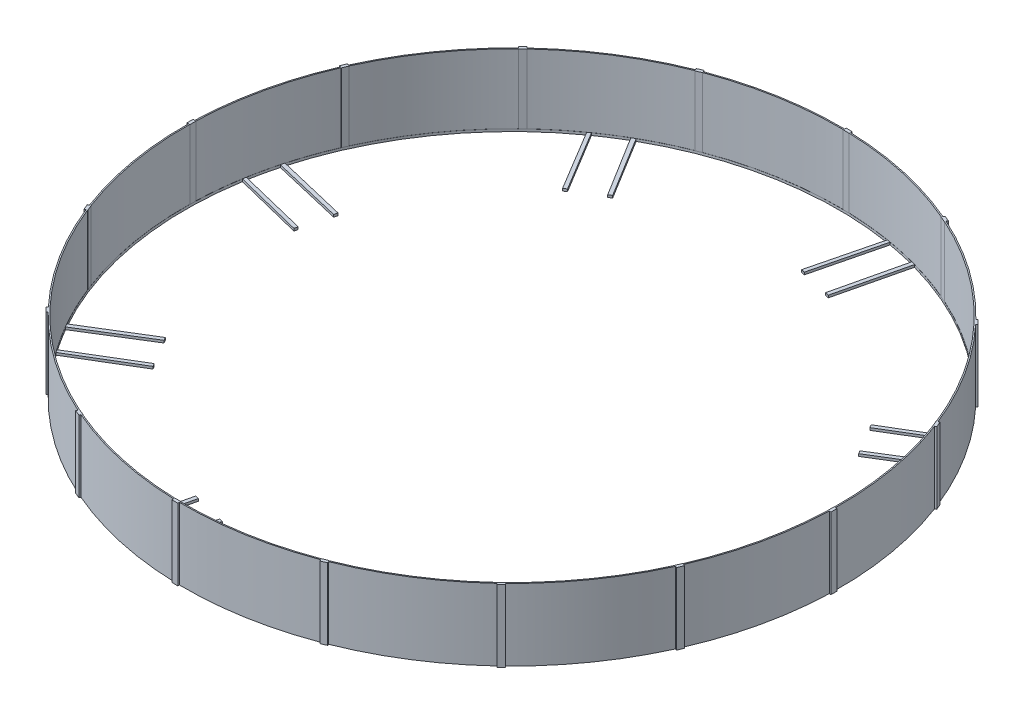
SolidWorks part; units mm, degrees
note: '?' marks a value the reader was unsure of.
ref_plane "Front Plane" through (0, 0, 0) normal (0, 0, 1) x (1, 0, 0)
ref_plane "Top Plane" through (0, 0, 0) normal (0, 1, 0) x (1, 0, 0)
ref_plane "Right Plane" through (0, 0, 0) normal (1, 0, 0) x (0, 0, -1)
sketch "Sketch2" plane through (0, 0, 0) normal (0, 1, 0) x (1, 0, 0)
  circle A0 centre (0, 0) radius 27500
  dimension "D1" = 55000
extrude "Boss-Extrude1" add sketch "Sketch2" along normal blind 6000 contours A0
sketch "Sketch3" plane through (0, 6000, 0) normal (0, 1, 0) x (1, 0, 0)
  circle A0 centre (0, 0) radius 27400
extrude "Cut-Extrude1" cut sketch "Sketch3" against normal blind 5800
ref_plane "Plane1" through (27500, 0, 0) normal (1, 0, 0) x (0, 0, -1)
sketch "Sketch6" plane through (27500, 0, 0) normal (1, 0, 0) x (0, 0, -1)
  line L0 (-387.6781, 6000) -> (-387.6781, 0)
  line L1 (-387.6781, 0) -> (-887.6781, 0)
  line L2 (-887.6781, 0) -> (-887.6781, 6000)
  line L3 (-887.6781, 6000) -> (-387.6781, 6000)
  dimension "D1" = 500
extrude "Boss-Extrude2" add sketch "Sketch6" along normal mid plane 250
pattern_circular "CirPattern1" count 16 over 360 about axis through (-0.0998, 0, -0.0022) along (0, 1, 0) of "Boss-Extrude2"
sketch "Sketch8" plane through (0, 200, 0) normal (0, 1, 0) x (1, 0, 0)
  circle A0 centre (0, 0) radius 27390
extrude "Cut-Extrude2" cut sketch "Sketch8" against normal blind 6227
sketch "Sketch10" plane through (0, 0, 0) normal (0, 1, 0) x (1, 0, 0)
  line L1 (5674.4495, 20624.9369) -> (5965.6783, 20552.9246)
  line L2 (5674.4495, 20624.9369) -> (7045.9309, 26466.0873)
  line L3 (7045.9309, 26466.0873) -> (7360.9751, 26388.3995)
  line L4 (5965.6783, 20552.9246) -> (7360.9751, 26388.3995)
  line L5 (5674.4495, 20624.9369) -> (7360.9751, 26388.3995) construction
  line L6 (7045.9309, 26466.0873) -> (5965.6783, 20552.9246) construction
  line L7 (4448.0345, 27106.7115) -> (4723.506, 27038.782)
  line L8 (4448.0345, 27106.7115) -> (2998.731, 21284.3821)
  line L9 (2998.731, 21284.3821) -> (3290.0036, 21212.5471)
  line L10 (4723.506, 27038.782) -> (3290.0036, 21212.5471)
  line L11 (4448.0345, 27106.7115) -> (3290.0036, 21212.5471) construction
  line L12 (2998.731, 21284.3821) -> (4723.506, 27038.782) construction
  circle A0 centre (0, 0) radius 27390 construction
  point P0 (6597.0321, 23909.272)
  point P9 (4306.9897, 24514.5962)
  dimension "D1" = 6000
  dimension "D2" = 300
  dimension "D3" = 300
  dimension "D4" = 5999.9683
  dimension "D5" = 27383.2877
extrude "Boss-Extrude3" add sketch "Sketch10" along normal blind 200
ref_axis "Axis1" through (0, -877.5, 0) along (0, 1, 0)?
pattern_circular "CirPattern2" count 8 over 360 about axis through (0, 0, 0) along (0, 1, 0) of "Boss-Extrude3"
fillet "Fillet1" radius 20 1 edges at (3144.3673, 200, -21248.4646)
fillet "Fillet2" radius 20 1 edges at (5820.0639, 200, -20588.9307)
